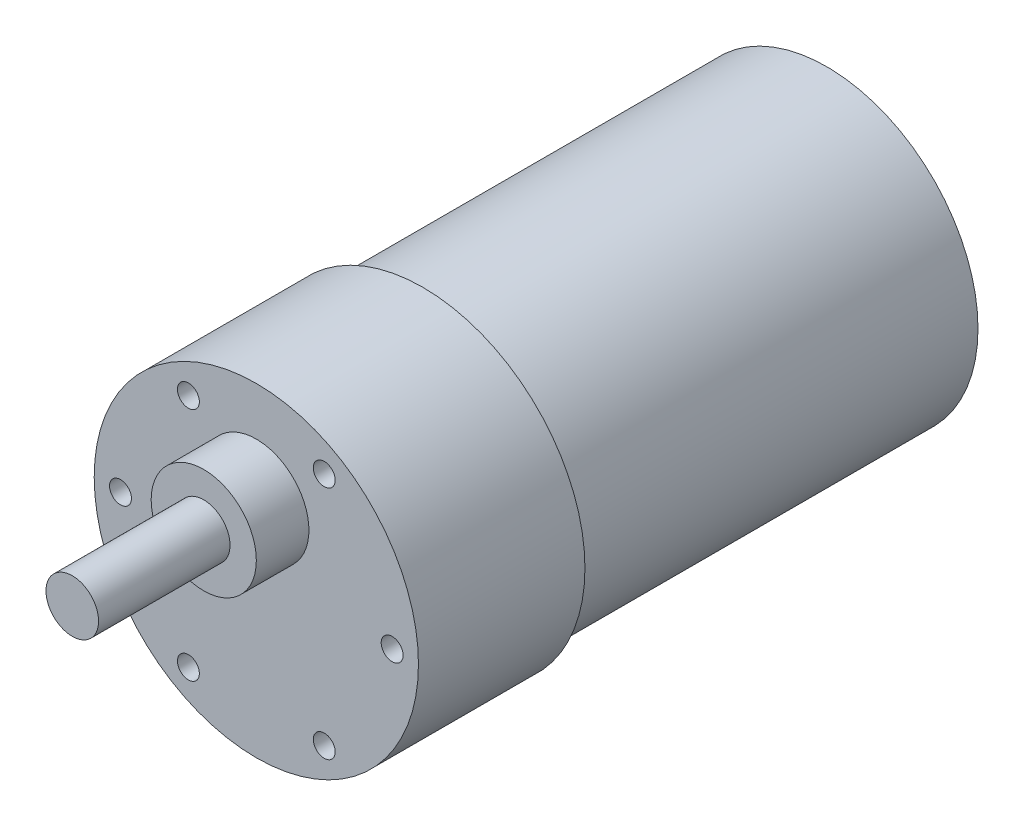
SolidWorks part; units mm, degrees
ref_plane "Front Plane" through (0, 0, 0) normal (0, 0, 1) x (1, 0, 0)
ref_plane "Top Plane" through (0, 0, 0) normal (0, 1, 0) x (1, 0, 0)
ref_plane "Right Plane" through (0, 0, 0) normal (1, 0, 0) x (0, 0, -1)
sketch "Sketch3" plane through (0, 0, 0) normal (1, 0, 0) x (0, 0, -1)
  line L0 (-4.9184, 0) -> (65.3745, 0) construction
  line L1 (0, 0) -> (0, 18.5)
  line L2 (0, 18.5) -> (19, 18.5)
  line L3 (19, 18.5) -> (19, 17.25)
  line L4 (19, 17.25) -> (49.8, 17.25)
  line L5 (49.8, 17.25) -> (65.1, 17.25)
  line L6 (65.1, 17.25) -> (65.1, 0)
  line L7 (65.1, 0) -> (0, 0)
  dimension "D1" = 30.8
  dimension "D2" = 15.3
  dimension "D3" = 34.5
  dimension "D4" = 37
  dimension "D5" = 19
revolve "Revolve1" add sketch "Sketch3" angle 360 about L0
sketch "Sketch4" plane through (0, 0, 0) normal (0, 0, 1) x (1, 0, 0)
  line L0 (0, 0) -> (18.5, 0) construction
  circle A0 centre (0, 7) radius 6
  circle A1 centre (0, 0) radius 18.5 construction
  circle A2 centre (0, 7) radius 3
  point P2 (15.5, 0)
  point P12 (7.75, -13.4234)
  point P13 (-7.75, -13.4234)
  point P14 (-15.5, 0)
  point P15 (-7.75, 13.4234)
  point P16 (7.75, 13.4234)
  point P17 (0, 0)
  dimension "D2" = 12
  dimension "D5" = 6
  dimension "D1" = 7
  dimension "D3" = 15.5
  dimension "D4" = 6
extrude "Boss-Extrude3" add sketch "Sketch4" along normal blind 6 contours A0
extrude "Boss-Extrude4" add sketch "Sketch4<3>" along normal blind 21 contours A2
sketch "Sketch4<3>" plane through (0, 0, 0) normal (0, 0, 1) x (1, 0, 0) same geometry as "Sketch4"
hole_wizard "Tap Drill for M3x0.5 Tap1" positions "Sketch7" profile "Sketch8" hole size "M3x0.5" standard "ANSI Metric"
sketch "Sketch7" plane through (0, 0, 0) normal (0, 0, 1) x (1, 0, 0)
  point P0 (-15.5, 0)
  point P3 (-7.75, 13.4234)
  point P6 (7.75, 13.4234)
  point P9 (15.5, 0)
  point P12 (7.75, -13.4234)
  point P15 (-7.75, -13.4234)
sketch "Sketch8" plane through (-15.5, 0, 0) normal (1, 0, 0) x (0, -1, 0)
  line L0 (0, 0) -> (0, 10.7511)
  line L1 (0, 10.7511) -> (1.25, 10)
  line L2 (1.25, 10) -> (1.25, 0)
  line L5 (1.25, 0) -> (0, 0)
  line L10 (0, 10.7511) -> (-1.25, 10) construction
  line L11 (0, -6.35) -> (0, 107.95) construction
  dimension "Hole Dia." = 2.5
  dimension "Hole Depth" = 10
  dimension "Drill Angle" = 118
